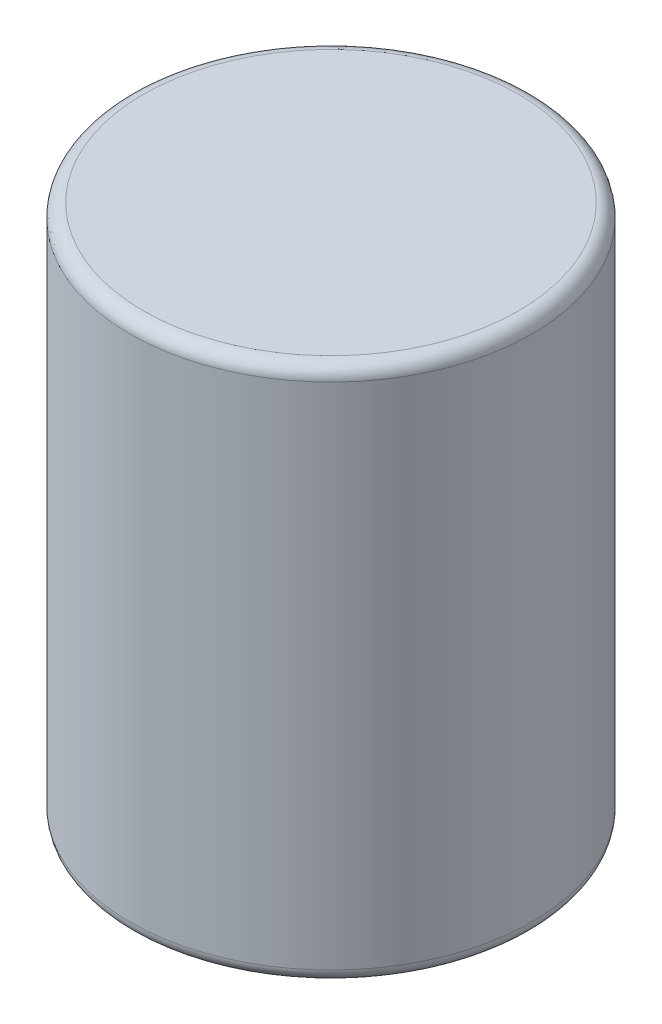
SolidWorks part; units mm, degrees
other "magnet"
ref_plane "Front Plane" through (0, 0, 0) normal (0, 0, 1) x (1, 0, 0)
ref_plane "Top Plane" through (0, 0, 0) normal (0, 1, 0) x (1, 0, 0)
ref_plane "Right Plane" through (0, 0, 0) normal (1, 0, 0) x (0, 0, -1)
sketch "Sketch1" plane through (0, 0, 0) normal (0, 1, 0) x (1, 0, 0)
  circle A0 centre (0, 0) radius 1.5
  dimension "D1" = 3
extrude "Boss-Extrude1" add sketch "Sketch1" along normal blind 4
fillet "Fillet1" radius 0.1 2 edges at (0, 0, 1.5) (0, 4, 1.5)
